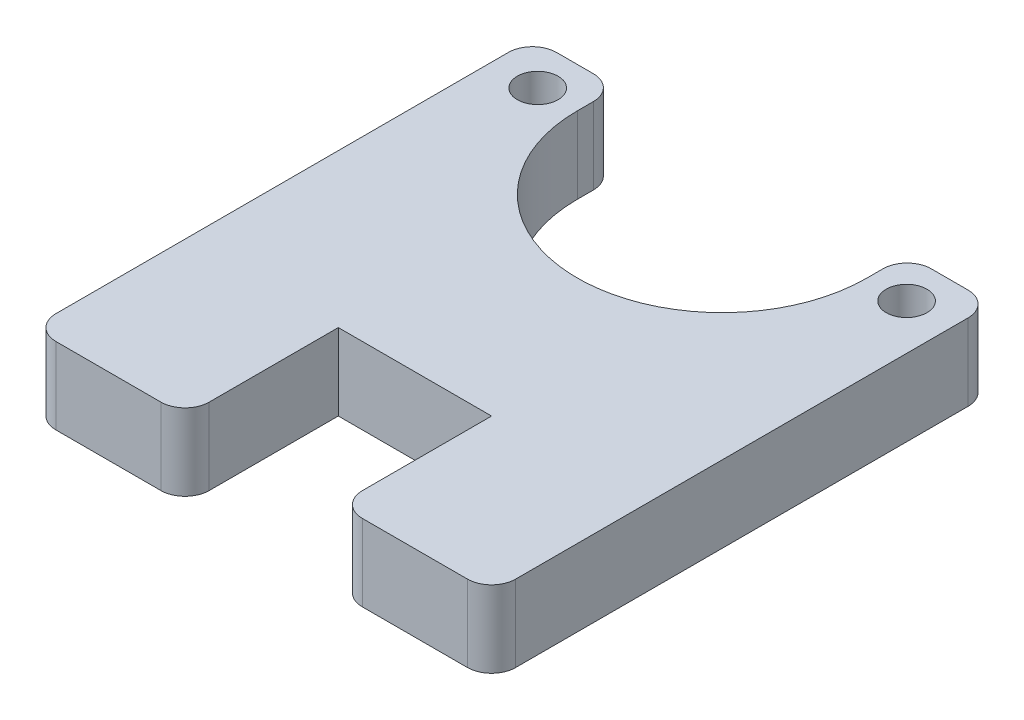
SolidWorks part; units mm, degrees
material "Beech"
ref_plane "Front Plane" through (0, 0, 0) normal (0, 0, 1) x (1, 0, 0)
ref_plane "Top Plane" through (0, 0, 0) normal (0, 1, 0) x (1, 0, 0)
ref_plane "Right Plane" through (0, 0, 0) normal (1, 0, 0) x (0, 0, -1)
sketch "Sketch1" plane through (0, 0, 0) normal (0, 1, 0) x (1, 0, 0)
  line L0 (0, 0) -> (0, 6)
  line L1 (0, 0) -> (19.05, 0)
  line L2 (0, 6) -> (19.05, 6)
  line L3 (19.05, 0) -> (19.05, 6)
  line L4 (0, 6) -> (0, 14.3936)
  line L5 (0, 6) -> (3.525, 6)
  line L6 (0, 14.3936) -> (3.525, 14.3936)
  line L7 (3.525, 6) -> (3.525, 14.3936)
  line L8 (19.05, 6) -> (19.05, 14.3936)
  line L9 (19.05, 6) -> (15.525, 6)
  line L10 (19.05, 14.3936) -> (15.525, 14.3936)
  line L11 (15.525, 6) -> (15.525, 14.3936)
  line L12 (0, 0) -> (6.35, 0)
  line L13 (0, 0) -> (0, -6.35)
  line L14 (6.35, 0) -> (6.35, -6.35)
  line L15 (0, -6.35) -> (6.35, -6.35)
  line L16 (19.05, 0) -> (12.7, 0)
  line L17 (19.05, 0) -> (19.05, -6.35)
  line L18 (12.7, 0) -> (12.7, -6.35)
  line L19 (19.05, -6.35) -> (12.7, -6.35)
  arc A0 (3.525, 12.7286) -> (15.525, 12.7286) centre (9.525, 12.7286) ccw
  circle A1 centre (17.1675, 12.7286) radius 0.845
  circle A2 centre (1.8825, 12.7286) radius 0.845
  point P8 (9.525, 6)
  dimension "D6" = 1.69
  dimension "D1" = 6
  dimension "D2" = 6.35
  dimension "D3" = 6.7286
  dimension "D4" = 6
  dimension "D5" = 1.665
  dimension "D7" = 1.6425
  dimension "D9" = 6.35
  dimension "D10" = 6.35
  dimension "D11" = 6.35
  dimension "D12" = 6.35
  dimension "D13" = 1.6425
extrude "Mount Body" add sketch "Sketch1" along normal blind 3.175 contours L2 L7 L6 L4 A2 | A0 L7 L2 L11 | L11 L2 L8 L10 A1 | L1 L3 L2 L0 | L13 L15 L14 L1 | L19 L17 L1 L18 region at (9.525, 0, -3) region at (3.175, 0, 3.175) region at (1.7527, 0, -9.9891) region at (3.6626, 0, -9.3643) region at (15.875, 0, 3.175) region at (17.2973, 0, -9.9891)
fillet "Fillet3" radius 1 8 edges at (19.05, 1.5875, 6.35) (12.7, 1.5875, 6.35) (6.35, 1.5875, 6.35) (0, 1.5875, 6.35) (19.05, 1.5875, -14.3936) (15.525, 1.5875, -14.3936) (3.525, 1.5875, -14.3936) (0, 1.5875, -14.3936)
equation "\"vigorwidth\"= 0.472441in"
equation "\"vigorflangewidth\"= 0.731102in"
equation "\"vigorflangelength\"= 0.131102in"
equation "\"vigorscrewsize\"= 0.066535in"
equation "\"vigorholeoffsetwid\"= 0.0646653in"
equation "\"vigorholeoffsetlen\"= 0.065551in"
equation "\"vigorflangedepth\"= 0.0901575in"
equation "\"vigordiscdepth\"= 0.0492126in"
equation "\"vigormotordepth\"= 1.12362in"
equation "\"vigortipdepth\"= 0.259055in"
equation "\"vigoraxlewidth\"= 0.173622in"
equation "\"vigorcutlen\"= 0.0480315in"
equation "\"vigoraxledepth\"= 0.159055in"
equation "\"D4@Sketch1\"=\"vigorwidth\"/2"
equation "\"TriggerRackOffset\"=6mm"
equation "\"D1@Sketch1\" = \"TriggerRackOffset\""
equation "\"TriggerSlotSizeInt\"=.25in"
equation "\"D10@Sketch1\" = \"TriggerSlotSizeInt\""
equation "\"D9@Sketch1\" = \"TriggerSlotSizeInt\""
equation "\"MotorMountLegLength\"=.25in"
equation "\"D11@Sketch1\"=\"MotorMountLegLength\""
equation "\"D12@Sketch1\"=\"MotorMountLegLength\""
equation "\"GearOffset\"=.264907in"
equation "\"D3@Sketch1\"=\"GearOffset\""
equation "\"D7@Sketch1\"=\"vigorholeoffsetwid\""
equation "\"D13@Sketch1\"=\"vigorholeoffsetwid\""
equation "\"D5@Sketch1\"=\"vigorflangelength\"/2"
equation "\"TriggerSlotSpacing\"=.25in"
equation "\"D2@Sketch1\" = \"TriggerSlotSpacing\""
equation "\"D6@Sketch1\"=\"vigorscrewsize\""
equation "\"CageLeftBottomEdge\"=22.11mm"
equation "\"CageLeftTopEdge\"=22.11mm"
equation "\"CageRightBottomEdge\"=21.63mm"
equation "\"CageRightTopEdge\"=21.63mm"
equation "\"CageHeight\"=86.04mm"
equation "\"CageLength\"=73.76mm"
equation "\"CageTopScrewClearance\"=10mm"
equation "\"CageBottomScrewClearance\"=25mm"
equation "\"CageLeftTopDepth\"= 11.65mm"
equation "\"CageLeftBottomDepth\"=11.11mm"
equation "\"CageLeftTopHeight\"=8.56175mm"
equation "\"CageLeftBottomHeight\"=16mm"
equation "\"CageRightTopDepth\"= 11.05mm"
equation "\"CageRightBottomDepth\"=10.58mm"
equation "\"CageRightTopHeight\"=9.6mm"
equation "\"CageRightBottomHeight\"=15.49mm"
equation "\"CageLeftTopChannelDepth\"=2.41908mm"
equation "\"CageLeftBottomChannelDepth\"=2.588mm"
equation "\"CageLeftChannelHeight\"=11.7mm"
equation "\"CageRightTopChannelDepth\"=2.32mm"
equation "\"CageRightBottomChannelDepth\"=2.318mm"
equation "\"CageRightChannelHeight\"=10mm"
equation "\"CageChanRelHeight\"=23.99mm"
equation "\"CageChanRelDepth\"=5.492mm"
equation "\"CageChamberRadius\"=16.261mm"
equation "\"CageScrewDiameter\"=4.8mm"
equation "\"CageSetScrewDiameter\"=3.5mm"
equation "\"CageAxleRadius\"=6.639mm"
equation "\"CageAxleKeyHeight\"=1.619mm"
equation "\"CageAxleKeyWidth\"=2.662mm"
equation "\"CageHoseWindowWidth\"=16.29mm"
equation "\"CageHoseWindowHeight\"=26.5mm"
equation "\"CageHoseWindow-Edge\"=8.89mm"
equation "\"CageScrew-VerticalEdge\"=5.0mm"
equation "\"CageScrew-HorizontalEdge\"=7.5mm"
equation "\"CageScrew-HoseCornerScrewEdge\"=4.45mm"
equation "\"CageAxle-BottomEdge\"=56.05mm"
equation "\"CageAxle-FrontEdge\"=46.03mm"
equation "\"CageBackSetScrew-Axle\"=40mm"
equation "\"CageFrontSetScrew-Axle\"=22mm"
equation "\"CageVelocityWindow-BackEdge\"=34.8mm"
equation "\"CageVelocityWindow-BottomEdge\"=27.55mm"
equation "\"CageVelocityWindowHeight\"=22.29mm"
equation "\"CageVelocityWindowWidth\"=12.61mm"
equation "\"TriggerSlot-BottomEdge\"=6.35mm"
equation "\"TriggerSlot-FrontEdge\"=15mm"
equation "\"TriggerSlotSize\"=6.7mm"
equation "\"TriggerMiniSlotWidth\"=3.5mm"
equation "\"TriggerRackWidth\"=6.5mm"
equation "\"gearhubintdiam\"=30mm"
equation "\"gearhubintwid\"=15mm"
equation "\"pandiscradius\"=14in"
equation "\"towermaterialwidth\"=.25in"
equation "\"towerslotlength\"=.5in"
equation "\"towermarkerspace\"=5in"
equation "\"towerslothorizoffset\"=1in"
equation "\"towerslothorizspacing\"=2in"
equation "\"towerslotvertoffset\"=3in"
equation "\"towerslotvertspacing\"=1in"
equation "\"towerheight\"=12in"
equation "\"towerupslot\"=1in"
equation "\"toweraxle\"=.5in"
equation "\"towerspeedwidth\"=2in"
equation "\"towerspeedheight\"=8in"
equation "\"towerspeedgap\"=2in"
equation "\"stepperouterrad\"=10mm"
equation "\"stepperscrewsize\"=3.45mm"
equation "\"stepperscrewc2c\"=49.5mm"
equation "\"stepperdepthoffset\"=24mm"
equation "\"stepperhorizoffset\"=22.91mm"
equation "\"stepperaxleflat\"=.037in"
equation "\"stepperaxlerad\"=0.11811024in"
equation "\"shaftslotOD\"=18.8mm"
equation "\"shaftslotID\"=13.28mm"
equation "\"shaftkeywidth\"=2.67mm"
equation "\"shaftkeydepth\"=1.8mm"
equation "\"shaftcollartotaldepth\"=12.5mm"
equation "\"shaftsquaredepth\"=6mm"
equation "\"shaftsetscrewsize\"=3.5mm"
equation "\"shaftkeytightdepth\"=1.85mm"
equation "\"shaftslottightID\"=12.78mm"
equation "\"shaftsetscrewoffset\"=9mm"
equation "\"cagecollartotaldepth\"=10mm"
equation "\"cagecollartotalwidth\"=35mm"
equation "\"cagecollarbasedepth\"=4mm"
equation "\"ajaxaxlesize\"=3.87mm"
equation "\"ajaxinnercut\"=2.3mm"
equation "\"ajaxwidth\"=6.1mm"
equation "\"ajaxdiametral\"=25.8854"
equation "\"ajaxcutoutdepth\"=2.3mm"
equation "\"ajax4020gap\"=29.5mm"
equation "\"ajax4010gap\"=24.5mm"
equation "\"ajax20hubbuffer\"=6.1mm"
equation "\"ajax20hubholeoffset\"=.19685in"
equation "\"ajax20hubholesize\"=.059055in"
equation "\"ajax20cutoutint\"=13.4mm"
equation "\"ajax40hubholesize\"=7.21mm"
equation "\"ajax40hubholeoffset\"=10mm"
equation "\"ajax40hubbuffer\"=8.9mm"
equation "\"ajax40cutoutint\"=32.6mm"
equation "\"bearingpandiscrad\"=6.8in"
equation "\"bearingpandiscang\"=48.75deg"
equation "\"bearingclearholedist\"=4.7345in"
equation "\"bearingclearholesize\"=.5in"
equation "\"bearingclearholeang\"=22.5deg"
equation "\"bearingmountholedist\"=4.25in"
equation "\"bearingwirehole\"=1.5in"
equation "\"no6diam\"=.146in"
equation "\"shortconangle\"=20deg"
equation "\"shortconlen\"=.875in"
equation "\"longconlen\"=1.25in"
equation "\"longconangle\"=15deg"
